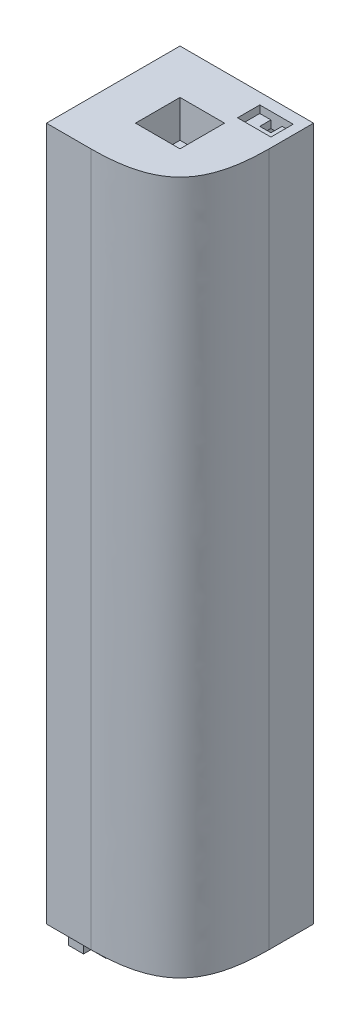
SolidWorks part; units mm, degrees
ref_plane "Front Plane" through (0, 0, 0) normal (0, 0, 1) x (1, 0, 0)
ref_plane "Top Plane" through (0, 0, 0) normal (0, 1, 0) x (1, 0, 0)
ref_plane "Right Plane" through (0, 0, 0) normal (1, 0, 0) x (0, 0, -1)
sketch "Sketch1" plane through (0, 0, 0) normal (0, 1, 0) x (1, 0, 0)
  line L1 (0, 0) -> (36, 0)
  line L2 (0, 0) -> (0, 36)
  line L3 (0, 36) -> (36, 36)
  line L4 (36, 0) -> (36, 36)
  dimension "D1" = 36
  dimension "D2" = 36
extrude "Boss-Extrude1" add sketch "Sketch1" along normal blind 186.9
fillet "Fillet1" radius 24 1 edges at (36, 93.45, 0) conic rho 0.55
sketch "Sketch2" plane through (0, 0, 0) normal (0, -1, 0) x (1, 0, 0)
  line L0 (36, -24) -> (36, -36) construction
  line L1 (0, -12.5) -> (14.28, -12.5)
  line L2 (0, -12.5) -> (0, -36)
  line L3 (0, -36) -> (14.28, -36)
  line L4 (14.28, -12.5) -> (14.28, -36)
  line L5 (0, 0) -> (12, 0) construction
  line L6 (0, -36) -> (0, 0) construction
  line L7 (36, -36) -> (0, -36) construction
  dimension "D1" = 21.72
  dimension "D2" = 12.5
  dimension "D3" = 0
  dimension "D4" = 0
extrude "Cut-Extrude1" cut sketch "Sketch2" against normal blind 27
sketch "Sketch3" plane through (0, 27, 0) normal (0, -1, 0) x (1, 0, 0)
  line L0 (0, -12.5) -> (0, -36) construction
  line L1 (0, -15) -> (11.78, -15)
  line L2 (0, -15) -> (0, -36)
  line L3 (0, -36) -> (11.78, -36)
  line L4 (11.78, -15) -> (11.78, -36)
  line L5 (0, -36) -> (14.28, -36) construction
  line L6 (14.28, -12.5) -> (0, -12.5) construction
  line L7 (14.28, -36) -> (14.28, -12.5) construction
  dimension "D1" = 2.5
  dimension "D2" = 2.5
extrude "Cut-Extrude2" cut sketch "Sketch3" against normal blind 8
sketch "Sketch4" plane through (0, 0, 0) normal (0, -1, 0) x (1, 0, 0)
  line L0 (36, -24) -> (36, -36) construction
  line L1 (0, 0) -> (12, 0) construction
  circle A0 centre (21, -15) radius 2
  dimension "D1" = 4
  dimension "D2" = 15
  dimension "D3" = 15
extrude "Cut-Extrude3" cut sketch "Sketch4" against normal blind 5
sketch "Sketch5" plane through (0, 0, 0) normal (0, -1, 0) x (1, 0, 0)
  line L0 (36, -24) -> (36, -36) construction
  line L1 (18, -28) -> (22, -28)
  line L2 (18, -28) -> (18, -32)
  line L3 (18, -32) -> (32, -32)
  line L4 (32, -28) -> (32, -32)
  line L5 (36, -36) -> (14.28, -36) construction
  line L7 (0, 0) -> (12, 0) construction
  line L8 (4, -2) -> (8, -2)
  line L9 (4, -2) -> (4, -10)
  line L10 (4, -10) -> (8, -10)
  line L11 (8, -2) -> (8, -4)
  line L13 (0, -12.5) -> (0, 0) construction
  line L14 (8, -8) -> (8, -10)
  line L15 (8, -4) -> (12, -4)
  line L17 (8, -8) -> (12, -8)
  line L18 (12, -4) -> (12, -8)
  line L20 (22, -28) -> (22, -24)
  line L21 (22, -24) -> (28, -24)
  line L22 (28, -28) -> (28, -24)
  line L23 (28, -28) -> (32, -28)
  dimension "D1" = 4
  dimension "D2" = 4
  dimension "D3" = 14
  dimension "D4" = 4
  dimension "D5" = 2
  dimension "D6" = 8
  dimension "D7" = 4
  dimension "D8" = 4
  dimension "D9" = 2
  dimension "D10" = 2
  dimension "D11" = 4
  dimension "D12" = 4
  dimension "D13" = 4
  dimension "D14" = 4
  dimension "D15" = 24
  dimension "D16" = 24
extrude "Boss-Extrude2" add sketch "Sketch5" along normal blind 4
sketch "Sketch6" plane through (0, 0, -36) normal (0, 0, -1) x (-1, 0, 0)
  line L0 (-36, 186.9) -> (0, 186.9) construction
  line L1 (-32, 182.9) -> (-26, 182.9)
  line L2 (-32, 182.9) -> (-32, 178.9)
  line L3 (-32, 178.9) -> (-26, 178.9)
  line L4 (-26, 182.9) -> (-26, 178.9)
  line L5 (-36, 186.9) -> (-36, 0) construction
  line L6 (0, 186.9) -> (0, 35) construction
  line L7 (-10, 182.9) -> (-4, 182.9)
  line L8 (-10, 182.9) -> (-10, 178.9)
  line L9 (-10, 178.9) -> (-4, 178.9)
  line L10 (-4, 182.9) -> (-4, 178.9)
  line L12 (-32, 162.9) -> (-26, 162.9)
  line L13 (-32, 162.9) -> (-32, 158.9)
  line L14 (-32, 158.9) -> (-26, 158.9)
  line L15 (-26, 162.9) -> (-26, 158.9)
  dimension "D1" = 4
  dimension "D2" = 4
  dimension "D3" = 6
  dimension "D4" = 4
  dimension "D5" = 6
  dimension "D6" = 4
  dimension "D7" = 4
  dimension "D8" = 4
  dimension "D9" = 16
  dimension "D10" = 4
extrude "Cut-Extrude4" cut sketch "Sketch6" against normal blind 9
sketch "Sketch7" plane through (0, 186.9, 0) normal (0, 1, 0) x (1, 0, 0)
  line L0 (36, 36) -> (0, 36) construction
  line L1 (27.5, 33) -> (30.5, 33)
  line L2 (27.5, 33) -> (27.5, 30)
  line L3 (27.5, 30) -> (30.5, 30)
  line L4 (30.5, 33) -> (30.5, 30)
  line L5 (36, 24) -> (36, 36) construction
  line L6 (0, 0) -> (12, 0) construction
  line L7 (12, 24) -> (24, 24)
  line L8 (12, 24) -> (12, 12)
  line L9 (12, 12) -> (24, 12)
  line L10 (24, 24) -> (24, 12)
  dimension "D1" = 3
  dimension "D2" = 3
  dimension "D3" = 3
  dimension "D4" = 5.5
  dimension "D5" = 12
  dimension "D6" = 12
  dimension "D7" = 12
  dimension "D8" = 12
extrude "Cut-Extrude5" cut sketch "Sketch7" against normal blind 10
sketch "Sketch8" plane through (0, 186.9, 0) normal (0, 1, 0) x (1, 0, 0)
  line L0 (30.5, 33) -> (27.5, 33) construction
  line L1 (33.5, 33) -> (24.5, 33)
  line L2 (33.5, 33) -> (33.5, 27)
  line L3 (33.5, 27) -> (24.5, 27)
  line L4 (24.5, 33) -> (24.5, 27)
  line L5 (30.5, 30) -> (30.5, 33) construction
  line L6 (27.5, 33) -> (27.5, 30) construction
  line L7 (27.5, 30) -> (30.5, 30) construction
  dimension "D1" = 0
  dimension "D2" = 3
  dimension "D3" = 3
  dimension "D4" = 3
extrude "Cut-Extrude6" cut sketch "Sketch8" against normal blind 2
